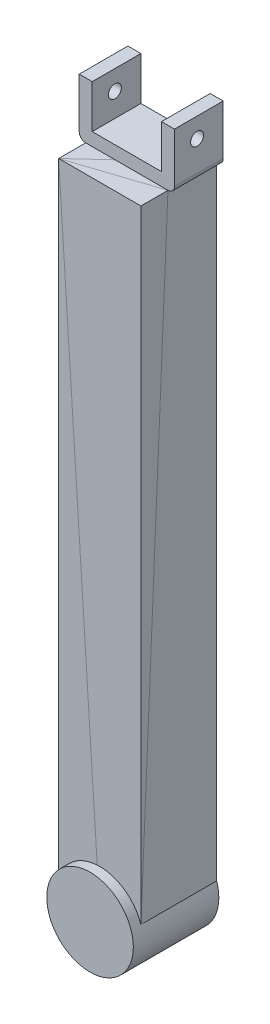
SolidWorks part; units mm, degrees
ref_plane "Front Plane" through (0, 0, 0) normal (0, 0, 1) x (1, 0, 0)
ref_plane "Top Plane" through (0, 0, 0) normal (0, 1, 0) x (1, 0, 0)
ref_plane "Right Plane" through (0, 0, 0) normal (1, 0, 0) x (0, 0, -1)
sketch "Sketch1" plane through (0, 0, 0) normal (0, 1, 0) x (1, 0, 0)
  line L1 (-19, 17.5) -> (19, 17.5)
  line L2 (-19, 17.5) -> (-19, -17.5)
  line L3 (-19, -17.5) -> (19, -17.5)
  line L4 (19, 17.5) -> (19, -17.5)
  line L5 (-19, 17.5) -> (19, -17.5) construction
  line L6 (-19, -17.5) -> (19, 17.5) construction
  point P0 (0, 0)
  dimension "D1" = 35
  dimension "D2" = 38
extrude "Boss-Extrude1" add sketch "Sketch1" against normal blind 295
sketch "Sketch2" plane through (0, 0, 0) normal (0, 0, 1) x (1, 0, 0)
  line L0 (-19, 0) -> (19, 0)
  line L1 (22, 3) -> (22, 26)
  line L2 (-22, 3) -> (-22, 26)
  line L3 (16, 6) -> (16, 26)
  line L4 (-16, 6) -> (16, 6)
  line L5 (-16, 6) -> (-16, 26)
  line L6 (-16, 26) -> (-22, 26)
  line L7 (16, 26) -> (22, 26)
  line L8 (-22, 0) -> (22, 0) construction
  line L9 (-22, 0) -> (-22, 26) construction
  line L10 (22, 0) -> (22, 26) construction
  arc A0 (-19, 0) -> (-22, 3) centre (-19, 3) cw
  arc A1 (19, 0) -> (22, 3) centre (19, 3) ccw
  dimension "D2" = 3
  dimension "D3" = 3
  dimension "D1" = 6
extrude "Boss-Extrude3" add sketch "Sketch2" against normal blind 17.5 and the other way blind 5 separate body
extrude "Boss-Extrude6" add sketch "Sketch1<3>" against normal blind 295
sketch "Sketch1<3>" plane through (0, 0, 0) normal (0, 1, 0) x (1, 0, 0) same geometry as "Sketch1"
ref_plane "Plane2" through (16, 0, 0) normal (-1, 0, 0) x (0, 0, 1)
sketch "Sketch3" plane through (16, 0, 0) normal (-1, 0, 0) x (0, 0, 1)
  circle A0 centre (-5.4606, 16.8963) radius 3
extrude "Cut-Extrude1" cut sketch "Sketch3" against normal up to vertex (6 mm away) up to point (22, 26, -17.5)
mirror "Mirror1" about plane through (0, 0, 0) normal (1, 0, 0) of "Cut-Extrude1"
sketch "Sketch5" plane through (0, 0, 0) normal (0, 0, 1) x (1, 0, 0)
  circle A0 centre (0, -293.7839) radius 20
extrude "Boss-Extrude8" add sketch "Sketch5" along normal blind 22 and the other way up to vertex (17.5 mm away) other way up to point (-19, -295, -17.5)
sketch "Sketch8" plane through (-19, 0, 0) normal (-1, 0, 0) x (0, 0, 1)
  line L0 (5, 0) -> (-17.5, 0) construction
  circle A0 centre (0, -85) radius 5
  dimension "D1" = 85
extrude "Cut-Extrude2" cut sketch "Sketch8" against normal blind 10
ref_point "Point1"
ref_point "Point2"
ref_axis "Axis1" through (16, 16.8963, -5.4606) along (-1, 0, 0)
sketch "Sketch9" plane through (-16, 0, 0) normal (1, 0, 0) x (0, 0, -1)
  line L0 (5.4606, 16.8963) -> (17.5, 16.8963) construction
  line L1 (17.5, 6) -> (17.5, 26) construction
ref_plane "Plane3" through (0, 0, 0) normal (1, 0, 0) x (0, 0, -1)
ref_plane "Plane4" through (0, 16.8963, 0) normal (0, 1, 0) x (1, 0, 0)
ref_axis "Axis3" through (0, 16.8963, 49.053) along (0, 0, -1)
sketch "Sketch11" plane through (0, 16.8963, 0) normal (0, 1, 0) x (1, 0, 0)
  line L1 (0, -49.053) -> (0, 76.8789) construction
  line L2 (16, 5.4606) -> (-16, 5.4606) construction
  point P0 (0, 5.4606)
